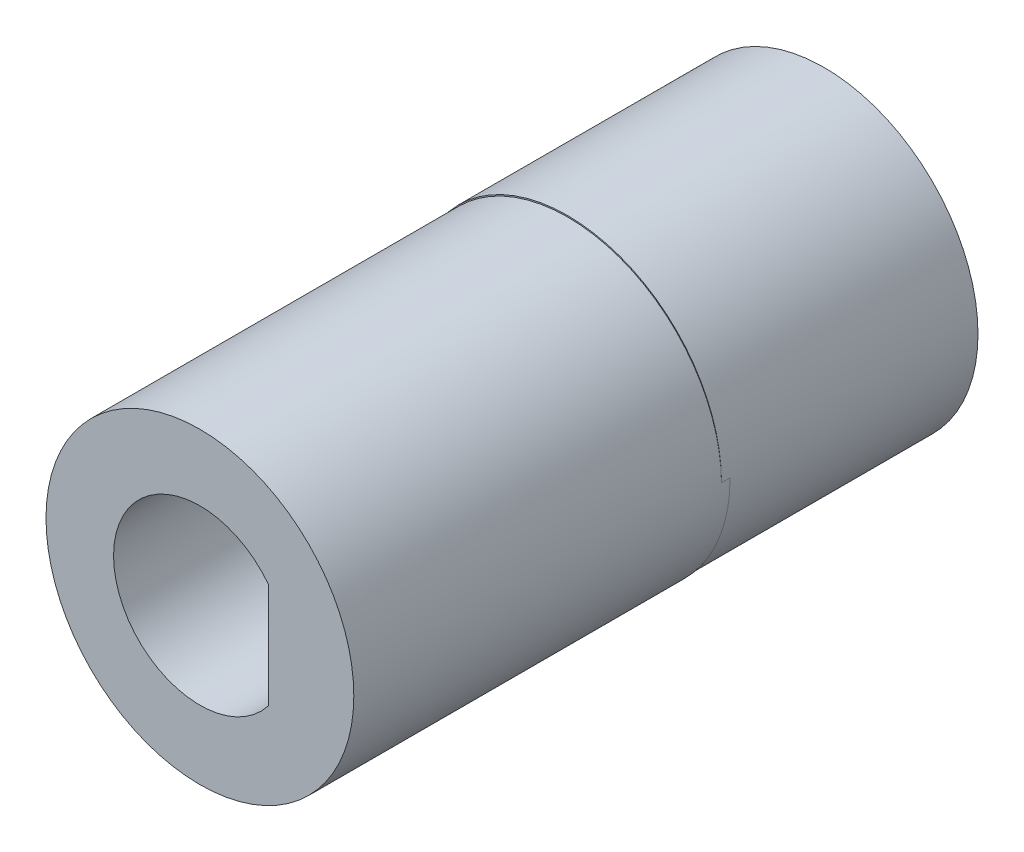
SolidWorks part; units mm, degrees
ref_plane "Front Plane" through (0, 0, 0) normal (0, 0, 1) x (1, 0, 0)
ref_plane "Top Plane" through (0, 0, 0) normal (0, 1, 0) x (1, 0, 0)
ref_plane "Right Plane" through (0, 0, 0) normal (1, 0, 0) x (0, 0, -1)
sketch "Sketch1" plane through (0, 0, 0) normal (0, 0, 1) x (1, 0, 0)
  line L0 (2.5, 1.7471) -> (2.5, -1.7471)
  circle A0 centre (0, 0) radius 3.05
  circle A1 centre (0, 0) radius 9
  point P6 (2.5, 0)
extrude "Boss-Extrude1" add sketch "Sketch1" against normal blind 8 contours A1 | A0
extrude "Boss-Extrude2" add sketch "Sketch1<3>" along normal blind 7 contours L0 A0 | A1 region at (-0.1274, 0, 0)
sketch "Sketch1<3>" plane through (0, 0, 0) normal (0, 0, 1) x (1, 0, 0) same geometry as "Sketch1"
ref_plane "Plane1" through (4.0165, 2.9778, 16.5) normal (0.5956, -0.8033, 0) x (-0.8033, -0.5956, 0)
sketch "Sketch3" plane through (0, 0, 16.5) normal (0, 0, -1) x (-1, 0, 0)
  line L0 (-4.0001, -3.0825) -> (-4.0001, 3.0825)
  circle A0 centre (0, 0) radius 5.05
  circle A1 centre (0, -0.0749) radius 9
  point P5 (-4.0001, 0)
  line M1 (-4.0165, 2.9778) -> (-3.9833, -3.0221)
  arc M3 (0.0277, -4.9999) -> (-4.0165, 2.9778) centre (0, 0) ccw
extrude "Boss-Extrude3" add sketch "Sketch3" against normal blind 12 separate body contours A1 A0 | L0 A0 M1 M3 region at (4.4264, -0.0112, 16.5) region at (8.7454, -0.0749, 16.5)
extrude "Boss-Extrude4" add sketch "Sketch3<3>" along normal blind 10 contours A1 A0 region at (8.7454, -0.0749, 16.5)
sketch "Sketch3<3>" plane through (0, 0, 16.5) normal (0, 0, -1) x (-1, 0, 0) same geometry as "Sketch3"
